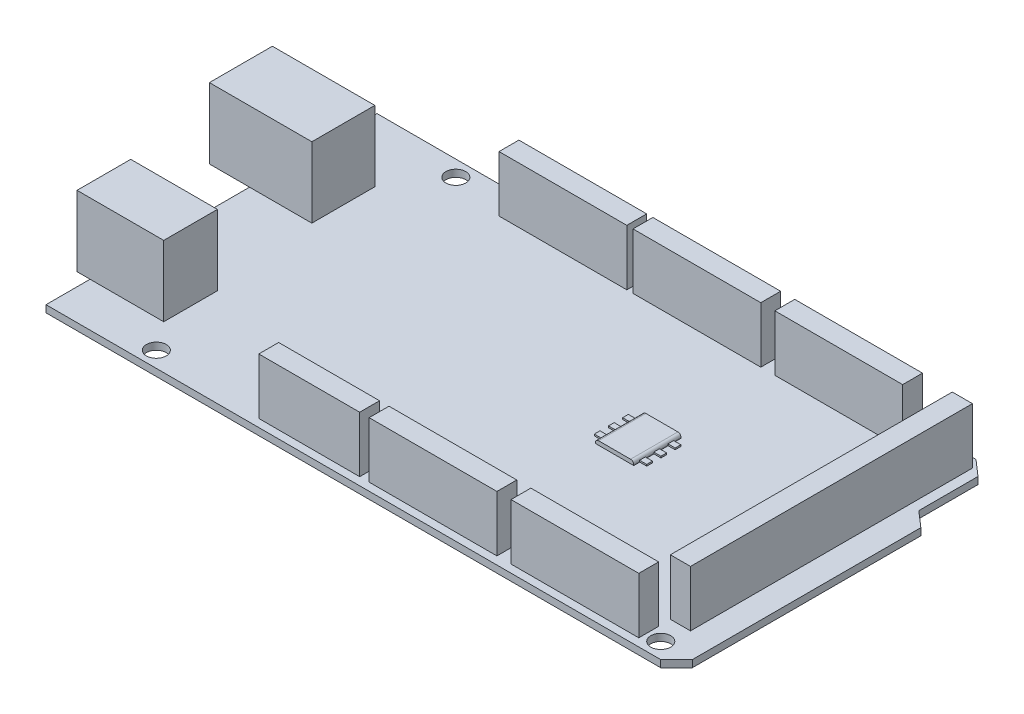
SolidWorks part; units mm, degrees
ref_plane "Front" through (0, 0, 0) normal (0, 0, 1) x (1, 0, 0)
ref_plane "Top" through (0, 0, 0) normal (0, 1, 0) x (1, 0, 0)
ref_plane "Right" through (0, 0, 0) normal (1, 0, 0) x (0, 0, -1)
sketch "Sketch2" plane through (0, 0, 0) normal (0, 1, 0) x (1, 0, 0)
  line L1 (0, 0) -> (101.6, 0)
  line L2 (0, 0) -> (0, 53.34)
  line L3 (0, 53.34) -> (101.6, 53.34)
  line L4 (101.6, 0) -> (101.6, 53.34)
  dimension "D1" = 101.6
  dimension "D2" = 53.34
extrude "Boss-Extrude1" add sketch "Sketch2" along normal blind 1.14
sketch "Sketch3" plane through (0, 1.14, 0) normal (0, 1, 0) x (1, 0, 0)
  line L0 (0, 26.67) -> (101.6, 26.67) construction
  line L1 (0, 53.34) -> (0, 0) construction
  line L2 (101.6, 0) -> (101.6, 53.34) construction
  line L3 (50.8, 0) -> (50.8, 53.34) construction
  line L4 (0, 0) -> (101.6, 0) construction
  line L5 (101.6, 53.34) -> (0, 53.34) construction
  circle A0 centre (15.24, 50.8) radius 1.6
  circle A1 centre (15.24, 2.54) radius 1.6
  dimension "D1" = 3.2
  dimension "D2" = 15.24
  dimension "D3" = 2.54
extrude "Cut-Extrude1" cut sketch "Sketch3" against normal through all
sketch "Sketch4" plane through (0, 1.14, 0) normal (0, 1, 0) x (1, 0, 0)
  line L0 (45.72, 52.07) -> (66.31, 52.07)
  line L1 (24.13, 52.07) -> (44.72, 52.07)
  line L2 (24.13, 52.07) -> (24.13, 48.87)
  line L3 (24.13, 48.87) -> (44.72, 48.87)
  line L4 (44.72, 52.07) -> (44.72, 48.87)
  line L5 (66.31, 52.07) -> (66.31, 48.87)
  line L6 (45.72, 48.87) -> (66.31, 48.87)
  line L7 (45.72, 52.07) -> (45.72, 48.87)
  line L8 (68.58, 52.07) -> (89.17, 52.07)
  line L9 (89.17, 52.07) -> (89.17, 48.87)
  line L10 (68.58, 48.87) -> (89.17, 48.87)
  line L11 (68.58, 52.07) -> (68.58, 48.87)
  line L12 (73.66, 4.47) -> (94.25, 4.47)
  line L13 (94.25, 4.47) -> (94.25, 1.27)
  line L14 (73.66, 1.27) -> (94.25, 1.27)
  line L15 (73.66, 4.47) -> (73.66, 1.27)
  line L16 (50.8, 4.47) -> (71.39, 4.47)
  line L17 (71.39, 4.47) -> (71.39, 1.27)
  line L18 (50.8, 1.27) -> (71.39, 1.27)
  line L19 (50.8, 4.47) -> (50.8, 1.27)
  line L20 (33.02, 4.47) -> (49.276, 4.47)
  line L21 (49.276, 4.47) -> (49.276, 1.27)
  line L22 (33.02, 1.27) -> (49.276, 1.27)
  line L23 (33.02, 4.47) -> (33.02, 1.27)
  line L25 (101.6, 53.34) -> (0, 53.34) construction
  line L26 (0, 0) -> (101.6, 0) construction
  circle A0 centre (15.24, 2.54) radius 1.6 construction
  circle A1 centre (15.24, 50.8) radius 1.6 construction
  point P24 (33.02, 2.87)
  dimension "D6" = 8.89
  dimension "D1" = 30.48
  dimension "D7" = 53.34
  dimension "D9" = 1.27
  dimension "D2" = 20.59
  dimension "D3" = 17.78
  dimension "D4" = 35.56
  dimension "D5" = 58.42
  dimension "D8" = 1.27
  dimension "D10" = 1.27
  dimension "D11" = 1.27
  dimension "D12" = 1.27
  dimension "D13" = 1.27
  dimension "D14" = 3.2
  dimension "D15" = 3.2
  dimension "D16" = 3.2
  dimension "D17" = 3.2
  dimension "D18" = 3.2
  dimension "D19" = 3.2
  dimension "D20" = 16.256
extrude "Boss-Extrude2" add sketch "Sketch4" along normal blind 9
sketch "Sketch5" plane through (0, 1.14, 0) normal (0, 1, 0) x (1, 0, 0)
  line L1 (101.6, 0) -> (99.06, 0)
  line L2 (101.6, 0) -> (101.6, 2.54)
  line L4 (99.06, 41.5843) -> (99.06, 51.1213)
  line L5 (101.6, 39.37) -> (99.06, 41.5843)
  line L6 (99.06, 0) -> (101.6, 0)
  line L7 (101.6, 39.37) -> (101.6, 53.34)
  line L9 (101.6, 0) -> (101.6, 2.54)
  line L10 (99.076, 51.1073) -> (96.536, 53.3216)
  line L11 (99.06, 0) -> (101.6, 2.54)
  line L12 (101.6, 53.34) -> (101.6055, 53.3418)
  line L14 (101.6, 53.3216) -> (101.6055, 53.3216)
  line L15 (96.536, 53.3216) -> (96.536, 57.5595)
  line L16 (96.536, 57.5595) -> (101.6055, 57.5595)
  line L17 (101.6055, 53.3216) -> (101.6055, 57.5595)
  line M21 (0, 0) -> (101.6, 0)
  line M22 (101.6, 0) -> (101.6, 53.34)
  dimension "D2" = 39.37
extrude "Cut-Extrude2" cut sketch "Sketch5" against normal through all contours L11 M21 M22 | L10 L4 L5 M22 region at (99.7723, 1.14, -50.3937) region at (100.7533, 1.14, -0.8467)
sketch "Sketch6" plane through (0, 1.14, 0) normal (0, 1, 0) x (1, 0, 0)
  line L0 (0, 0) -> (99.06, 0) construction
  line L1 (96.536, 53.34) -> (0, 53.34) construction
  circle A0 centre (96.52, 2.54) radius 1.6
  circle A1 centre (91.44, 50.8) radius 1.6
  circle A2 centre (15.24, 2.54) radius 1.6 construction
  circle A3 centre (15.24, 50.8) radius 1.6 construction
  dimension "D1" = 3.2
  dimension "D2" = 3.2
  dimension "D4" = 2.54
  dimension "D5" = 81.28
  dimension "D6" = 76.2
  dimension "D3" = 2.54
extrude "Cut-Extrude3" cut sketch "Sketch6" against normal through all
sketch "Sketch7" plane through (0, 1.14, 0) normal (0, 1, 0) x (1, 0, 0)
  line L1 (94.2041, 6.4033) -> (97.4493, 6.4033)
  line L2 (94.2041, 6.4033) -> (94.2041, 51.8366)
  line L3 (94.2041, 51.8366) -> (97.4493, 51.8366)
  line L4 (97.4493, 6.4033) -> (97.4493, 51.8366)
extrude "Boss-Extrude3" add sketch "Sketch7" along normal blind 9
sketch "Sketch8" plane through (0, 1.14, 0) normal (0, 1, 0) x (1, 0, 0)
  line L0 (0, 53.34) -> (0, 0) construction
  line L1 (-6.47, 32.7987) -> (10.04, 32.7987)
  line L2 (-6.47, 32.7987) -> (-6.47, 42.9489)
  line L3 (-6.47, 42.9489) -> (10.04, 42.9489)
  line L4 (10.04, 32.7987) -> (10.04, 42.9489)
  line L6 (-2.1, 7.1016) -> (11.87, 7.1016)
  line L7 (-2.1, 7.1016) -> (-2.1, 15.752)
  line L8 (-2.1, 15.752) -> (11.87, 15.752)
  line L9 (11.87, 7.1016) -> (11.87, 15.752)
  dimension "D1" = 6.47
  dimension "D2" = 2.1
  dimension "D3" = 13.97
  dimension "D4" = 16.51
extrude "Boss-Extrude4" add sketch "Sketch8" along normal blind 11.36
sketch "Sketch9" plane through (-2.1, 0, 0) normal (-1, 0, 0) x (0, 0, 1)
  line L0 (-11.4268, 12.5) -> (-11.4268, 1.14) construction
  line L1 (-15.752, 12.5) -> (-7.1016, 12.5) construction
  line L2 (-15.752, 1.14) -> (-7.1016, 1.14) construction
  circle A0 centre (-11.4268, 7.8705) radius 3.2177
  circle A1 centre (-11.4268, 7.8705) radius 1.1827
extrude "Cut-Extrude4" cut sketch "Sketch9" against normal blind 11.36
sketch "Sketch10" plane through (-6.47, 0, 0) normal (-1, 0, 0) x (0, 0, 1)
  line L0 (-37.8738, 12.5) -> (-37.8738, 1.14) construction
  line L1 (-42.9489, 12.5) -> (-32.7987, 12.5) construction
  line L2 (-42.9489, 1.14) -> (-32.7987, 1.14) construction
  line L4 (-41.0488, 9.6378) -> (-34.6988, 9.6378)
  line L5 (-41.0488, 9.6378) -> (-41.0488, 4.0757)
  line L6 (-41.0488, 4.0757) -> (-34.6988, 4.0757)
  line L7 (-34.6988, 9.6378) -> (-34.6988, 4.0757)
  line L8 (-40.4406, 6.0584) -> (-35.2398, 6.0584)
  line L9 (-40.4406, 6.0584) -> (-40.4406, 4.6059)
  line L10 (-40.4406, 4.6059) -> (-35.2398, 4.6059)
  line L11 (-35.2398, 6.0584) -> (-35.2398, 4.6059)
  dimension "D1" = 6.35
  dimension "D2" = 3.175
extrude "Cut-Extrude5" cut sketch "Sketch10" against normal blind 11.36
chamfer "Chamfer1" distance 1.524 angle 45 2 edges at (-0.79, 9.6378, -34.6988) (-0.79, 9.6378, -41.0488)
sketch "Sketch11" plane through (0, 1.14, 0) normal (0, 1, 0) x (1, 0, 0)
  line L0 (96.536, 53.34) -> (0, 53.34) construction
  line L1 (63.63, 32.52) -> (69.8062, 32.52)
  line L2 (63.63, 32.52) -> (63.63, 24.9)
  line L3 (63.63, 24.9) -> (69.8062, 24.9)
  line L4 (69.8062, 32.52) -> (69.8062, 24.9)
  circle A0 centre (15.24, 50.8) radius 1.6 construction
  dimension "D1" = 48.39
  dimension "D2" = 20.82
  dimension "D3" = 7.62
extrude "Boss-Extrude5" add sketch "Sketch11" along normal blind 0.635
sketch "Sketch12" plane through (0, 1.14, 0) normal (0, 1, 0) x (1, 0, 0)
  line L0 (62.4818, 29.0669) -> (62.4818, 28.1512)
  line L1 (62.4818, 31.3529) -> (70.9386, 31.3529)
  line L2 (62.4818, 31.3529) -> (62.4818, 30.4372)
  line L3 (62.4818, 30.4372) -> (70.9386, 30.4372)
  line L4 (70.9386, 31.3529) -> (70.9386, 30.4372)
  line L5 (62.4818, 29.0669) -> (70.9386, 29.0669)
  line L6 (70.9386, 29.0669) -> (70.9386, 28.1512)
  line L7 (62.4818, 28.1512) -> (70.9386, 28.1512)
  line L8 (62.4818, 26.7809) -> (62.4818, 25.8652)
  line L9 (62.4818, 26.7809) -> (70.9386, 26.7809)
  line L10 (70.9386, 26.7809) -> (70.9386, 25.8652)
  line L11 (62.4818, 25.8652) -> (70.9386, 25.8652)
  dimension "D1" = 3
extrude "Boss-Extrude6" add sketch "Sketch12" along normal blind 0.254
fillet "Fillet1" radius 0.508 2 edges at (69.8062, 1.775, -28.71) (63.63, 1.775, -28.71)
